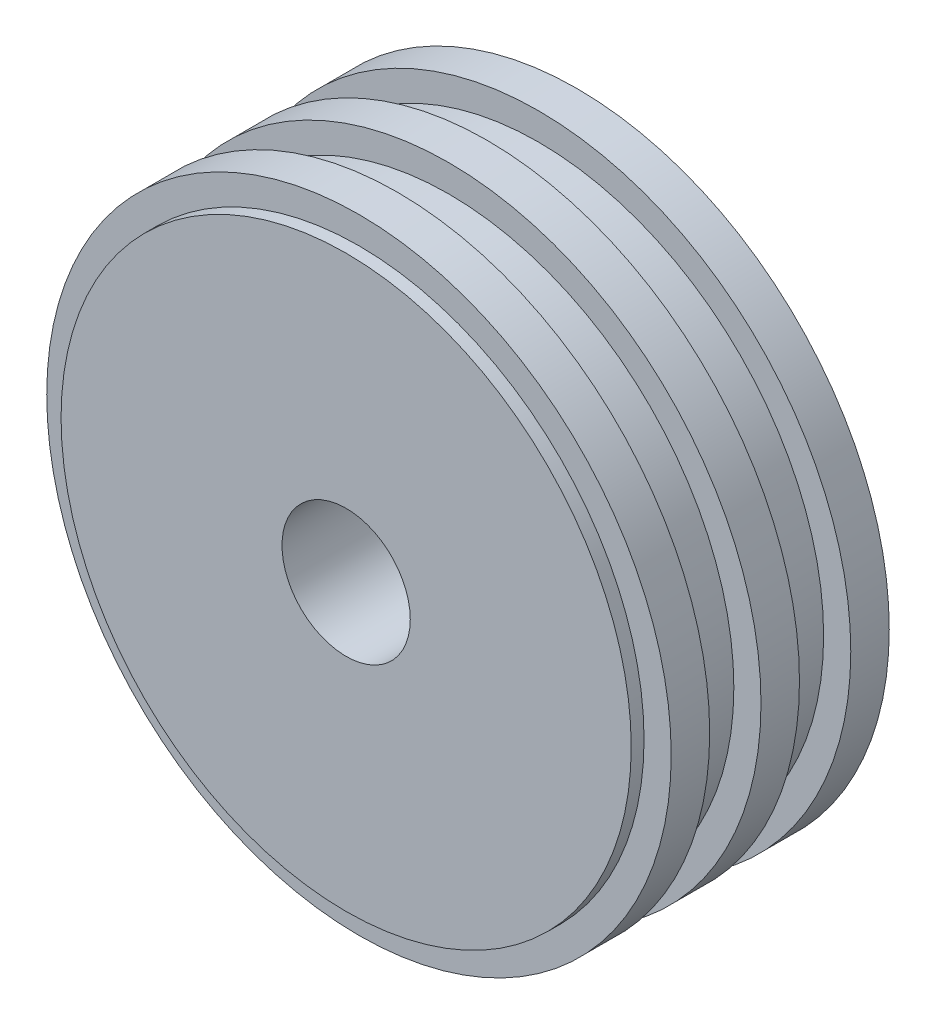
SolidWorks part; units mm, degrees
ref_plane "Front Plane" through (0, 0, 0) normal (0, 0, 1) x (1, 0, 0)
ref_plane "Top Plane" through (0, 0, 0) normal (0, 1, 0) x (1, 0, 0)
ref_plane "Right Plane" through (0, 0, 0) normal (1, 0, 0) x (0, 0, -1)
sketch "Sketch1" plane through (0, 0, 0) normal (0, 0, 1) x (1, 0, 0)
  circle A0 centre (0, 0) radius 15
  circle A1 centre (0, 0) radius 66.675
  dimension "D1" = 133.35
  dimension "D2" = 30
extrude "Boss-Extrude1" add sketch "Sketch1" against normal blind 57
ref_plane "Plane1" through (0, 0, -3) normal (0, 0, 1) x (1, 0, 0)
sketch "Sketch2" plane through (0, 0, -3) normal (0, 0, 1) x (1, 0, 0)
  circle A0 centre (0, 0) radius 66.675 construction
  circle A1 centre (0, 0) radius 66.675
  circle A2 centre (0, 0) radius 73.025
  dimension "D1" = 146.05
extrude "Boss-Extrude2" add sketch "Sketch2" against normal blind 9
ref_axis "Axis1" through (0, 0, -57) along (0, 0, 1)
pattern_linear "LPattern1" count 3 spacing 21 along (0, 0, -1) of "Boss-Extrude2"
